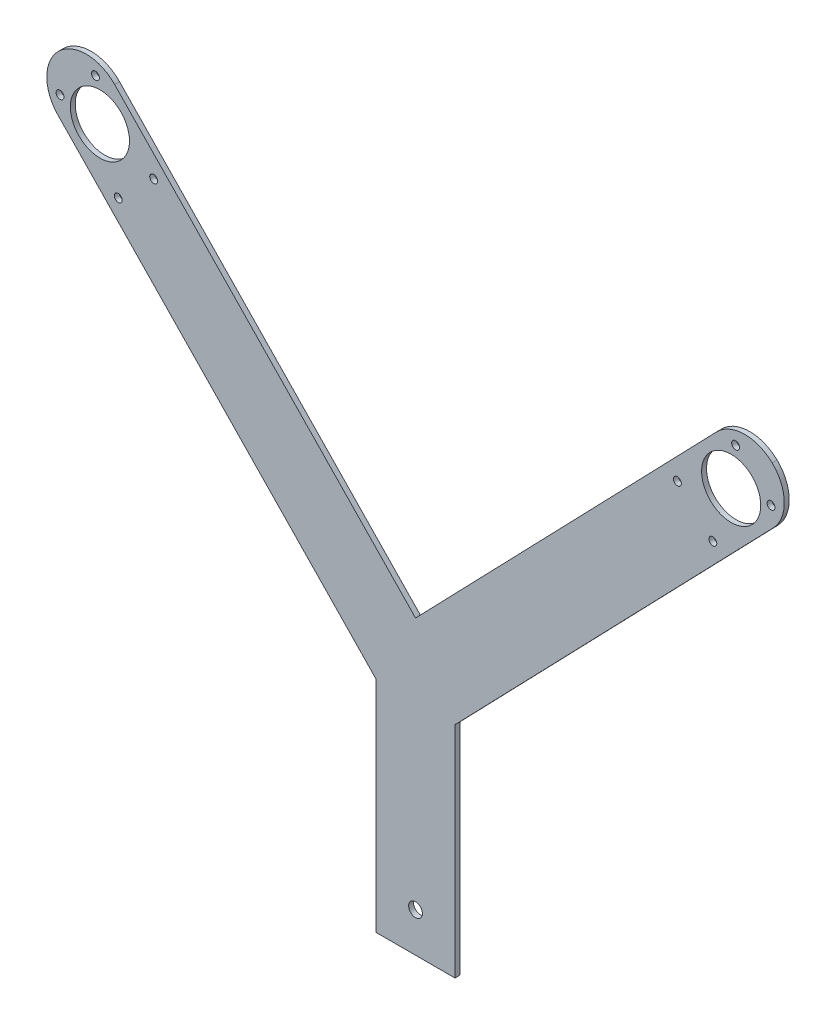
SolidWorks part; units mm, degrees
ref_plane "Front Plane" through (0, 0, 0) normal (0, 0, 1) x (1, 0, 0)
ref_plane "Top Plane" through (0, 0, 0) normal (0, 1, 0) x (1, 0, 0)
ref_plane "Right Plane" through (0, 0, 0) normal (1, 0, 0) x (0, 0, -1)
sketch "Sketch1" plane through (0, 0, 0) normal (0, 0, 1) x (1, 0, 0)
  line L0 (0, 0) -> (50.8, 0)
  line L1 (50.8, 0) -> (50.8, 141.3009)
  line L2 (50.8, 141.3009) -> (273.4748, 371.8874)
  line L3 (0, 0) -> (0, 141.3009)
  line L4 (0, 141.3009) -> (-222.6748, 371.8874)
  line L5 (-222.6748, 371.8874) -> (-186.1323, 407.1761)
  line L6 (-186.1323, 407.1761) -> (25.4, 188.1279)
  line L7 (25.4, 188.1279) -> (236.9323, 407.1761)
  line L8 (236.9323, 407.1761) -> (273.4748, 371.8874)
  circle A0 centre (25.4, 800.087) radius 406.4 construction
  point P3 (-80.3662, 297.652)
  point P13 (58.3779, 354.3853)
  point P14 (152.3362, 314.1592)
  point P15 (25.4, 347.691)
  point P16 (93.8813, 613.8405)
  point P17 (0, 0)
  point P18 (0, 0)
  point P19 (0, 0)
  dimension "D1" = 812.8
  dimension "D3" = 50.8
  dimension "D4" = 50.8
  dimension "D5" = 50.8
  dimension "D6" = 88
extrude "Boss-Extrude1" add sketch "Sketch1" along normal blind 3.175 contours L1 L2 L8 L7 L6 L5 L4 L3 L0
sketch "Sketch2" plane through (0, 0, 3.175) normal (0, 0, 1) x (1, 0, 0)
  line L0 (50.8, 141.3009) -> (273.4748, 371.8874) construction
  line L1 (-186.1323, 407.1761) -> (25.4, 188.1279) construction
  line L2 (236.9323, 407.1761) -> (273.4748, 371.8874) construction
  line L3 (-222.6748, 371.8874) -> (-186.1323, 407.1761) construction
  line L4 (50.8, 0) -> (50.8, 141.3009) construction
  line L5 (0, 0) -> (50.8, 0) construction
  circle A0 centre (228.7371, 362.1249) radius 19.05
  circle A1 centre (-177.9371, 362.1249) radius 19.05
  circle A2 centre (25.4, 25.4) radius 4.445
  point P18 (237.5592, 371.2605)
  dimension "D2" = 38.1
  dimension "D3" = 25.4
  dimension "D4" = 38.1
  dimension "D5" = 38.1
  dimension "D6" = 38.1
  dimension "D8" = 8.89
  dimension "D9" = 25.4
  dimension "D1" = 25.4
  dimension "D7" = 25.4
extrude "Cut-Extrude1" cut sketch "Sketch2" against normal through all
fillet "Fillet1" radius 25.4 4 edges at (273.4748, 371.8874, 1.5875) (236.9323, 407.1761, 1.5875) (-222.6748, 371.8874, 1.5875) (-186.1323, 407.1761, 1.5875)
sketch "Sketch3" plane through (0, 0, 3.175) normal (0, 0, 1) x (1, 0, 0)
  line L0 (231.5933, 387.6148) -> (194.0991, 348.7885) construction
  line L1 (194.0991, 348.7885) -> (216.9381, 326.7331) construction
  line L2 (216.9381, 326.7331) -> (254.4323, 365.5594) construction
  line L3 (254.4323, 365.5594) -> (231.5933, 387.6148) construction
  line L4 (50.8, 141.3009) -> (255.8305, 353.6162) construction
  circle A0 centre (231.5933, 387.6148) radius 2.54
  circle A1 centre (254.4323, 365.5594) radius 2.54
  circle A2 centre (216.9381, 326.7331) radius 2.54
  circle A3 centre (194.0991, 348.7885) radius 2.54
  circle A6 centre (228.7371, 362.1249) radius 19.05 construction
  dimension "D1" = 5.08
  dimension "D2" = 31.75
  dimension "D3" = 33.655
  dimension "D4" = 53.975
extrude "Cut-Extrude2" cut sketch "Sketch3" against normal through all
ref_plane "Plane1" through (25.4, 0, 0) normal (-1, 0, 0) x (0, 0, 1)
mirror "Mirror1" about plane through (25.4, 0, 0) normal (-1, 0, 0) of "Cut-Extrude2"
